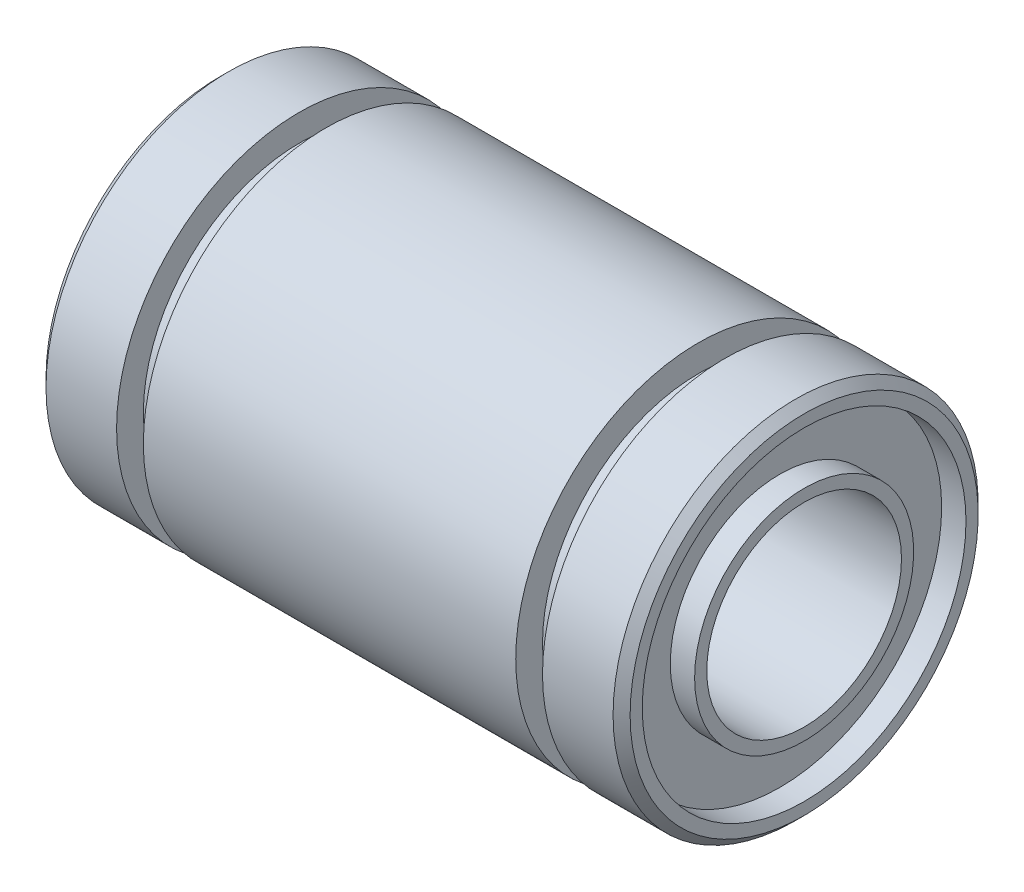
SolidWorks part; units mm, degrees
material "1060 Alloy"
ref_plane "Front Plane" through (0, 0, 0) normal (0, 0, 1) x (1, 0, 0)
ref_plane "Top Plane" through (0, 0, 0) normal (0, 1, 0) x (1, 0, 0)
ref_plane "Right Plane" through (0, 0, 0) normal (1, 0, 0) x (0, 0, -1)
sketch "Sketch1" plane through (0, 0, 0) normal (0, 0, 1) x (1, 0, 0)
  line L0 (-45.6895, 0) -> (45.6895, 0) construction
  line L1 (-11.65, 7.5) -> (-8.75, 7.5)
  line L2 (-8.75, 7.5) -> (-8.75, 6.4)
  line L3 (-8.75, 6.4) -> (-7.65, 6.4)
  line L4 (-7.65, 6.4) -> (-7.65, 7.5)
  line L5 (-7.65, 7.5) -> (7.65, 7.5)
  line L6 (0, 45.6895) -> (0, -45.6895) construction
  line L7 (-11.65, 7.5) -> (-12, 7.15)
  line L8 (-12, 7.15) -> (-12, 6.65)
  line L9 (-12, 6.65) -> (-11, 6.65)
  line L10 (-11, 6.65) -> (-11, 4.5)
  line L11 (-11, 4.5) -> (-12, 4.5)
  line L12 (-12, 4.5) -> (-12, 4)
  line L13 (-12, 4) -> (12, 4)
  line L14 (12, 4.5) -> (12, 4)
  line L15 (11, 4.5) -> (12, 4.5)
  line L16 (11, 6.65) -> (11, 4.5)
  line L17 (12, 6.65) -> (11, 6.65)
  line L18 (12, 7.15) -> (12, 6.65)
  line L19 (11.65, 7.5) -> (12, 7.15)
  line L20 (7.65, 6.4) -> (7.65, 7.5)
  line L21 (8.75, 6.4) -> (7.65, 6.4)
  line L22 (8.75, 7.5) -> (8.75, 6.4)
  line L23 (11.65, 7.5) -> (8.75, 7.5)
  point P19 (0, 4)
  point P26 (0, 7.5)
  dimension "D1" = 45
  dimension "D2" = 1.1
  dimension "D3" = 0.5
  dimension "L" = 19
  dimension "B" = 13.5
  dimension "W" = 1.1
  dimension "D" = 6
  dimension "D_1" = 5.75
  dimension "D4" = 0.5
  dimension "dr" = 3
  dimension "D5" = 1
revolve "Revolve1" add sketch "Sketch1" angle 360 about L0 region at (0, 5.7195, 0)
equation "\"D\"=15"
equation "\"D1\"=14.3"
equation "\"dr\"=8"
equation "\"L\"=24"
equation "\"B\"=17.5"
equation "\"W\"=1.1"
equation "\"L@Sketch1\"= \"L\""
equation "\"B@Sketch1\"= \"B\""
equation "\"W@Sketch1\"= \"W\""
equation "\"dr@Sketch1\"= \"dr\" * 0.5"
equation "\"D@Sketch1\" = \"D\" * 0.5"
equation "\"D_1@Sketch1\" = \"D1\" * 0.5"
